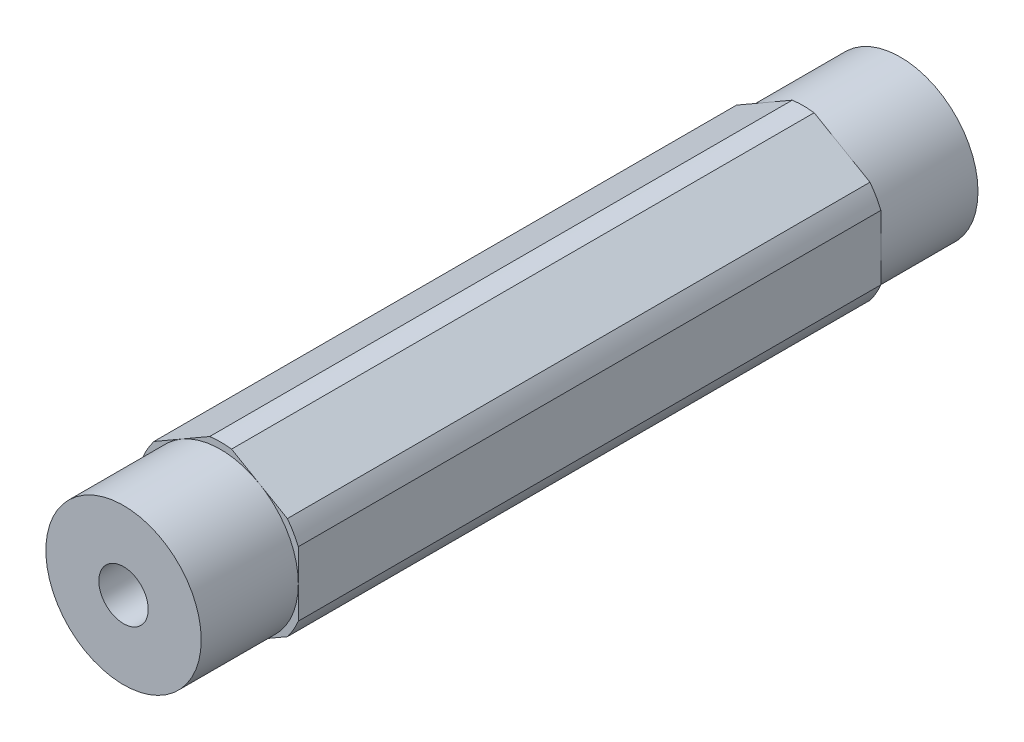
SolidWorks part; units mm, degrees
material "6061-T6 (SS)"
ref_plane "Front Plane" through (0, 0, 0) normal (0, 0, 1) x (1, 0, 0)
ref_plane "Top Plane" through (0, 0, 0) normal (0, 1, 0) x (1, 0, 0)
ref_plane "Right Plane" through (0, 0, 0) normal (1, 0, 0) x (0, 0, -1)
sketch "Sketch1" plane through (0, 0, 0) normal (0, 0, 1) x (1, 0, 0)
  line L0 (0, 7.3323) -> (-0.893, 6.8168) construction
  line L1 (-0.893, 6.8168) -> (-5.457, 4.1818)
  line L2 (-6.35, 2.635) -> (-6.35, -2.635)
  line L3 (-5.457, -4.1818) -> (-0.893, -6.8168)
  line L4 (0.893, -6.8168) -> (5.457, -4.1818)
  line L5 (6.35, -2.635) -> (6.35, 2.635)
  line L6 (5.457, 4.1818) -> (0.893, 6.8168)
  line L7 (0.893, 6.8168) -> (0, 7.3323) construction
  circle A0 centre (0, 0) radius 6.35 construction
  arc A2 (-6.35, -2.635) -> (-5.457, -4.1818) centre (0, 0) ccw
  arc A3 (-5.457, 4.1818) -> (-6.35, 2.635) centre (0, 0) ccw
  arc A4 (0.893, 6.8168) -> (-0.893, 6.8168) centre (0, 0) ccw
  arc A5 (-0.893, -6.8168) -> (0.893, -6.8168) centre (0, 0) ccw
  arc A6 (5.457, -4.1818) -> (6.35, -2.635) centre (0, 0) ccw
  arc A7 (6.35, 2.635) -> (5.457, 4.1818) centre (0, 0) ccw
  dimension "D1" = 12.7
  dimension "D2" = 13.75
extrude "Boss-Extrude1" add sketch "Sketch1" along normal mid plane 63.5
sketch "Sketch3" plane through (0, 0, 31.75) normal (0, 0, 1) x (1, 0, 0)
  circle A0 centre (0, 0) radius 2.0193
  dimension "D1" = 4.0386
extrude "Cut-Extrude1" cut sketch "Sketch3" against normal through all
sketch "Sketch7" plane through (0, 0, 31.75) normal (0, 0, 1) x (1, 0, 0)
  circle A0 centre (0, 0) radius 6.35
  circle A1 centre (0, 0) radius 6.875
  arc A2 (0.893, 6.8168) -> (-0.893, 6.8168) centre (0, 0) ccw construction
  dimension "D1" = 12.7
extrude "Cut-Extrude2" cut sketch "Sketch7" against normal blind 7.9375
mirror "Mirror1" about plane through (0, 0, 0) normal (0, 0, 1) of "Cut-Extrude2"
